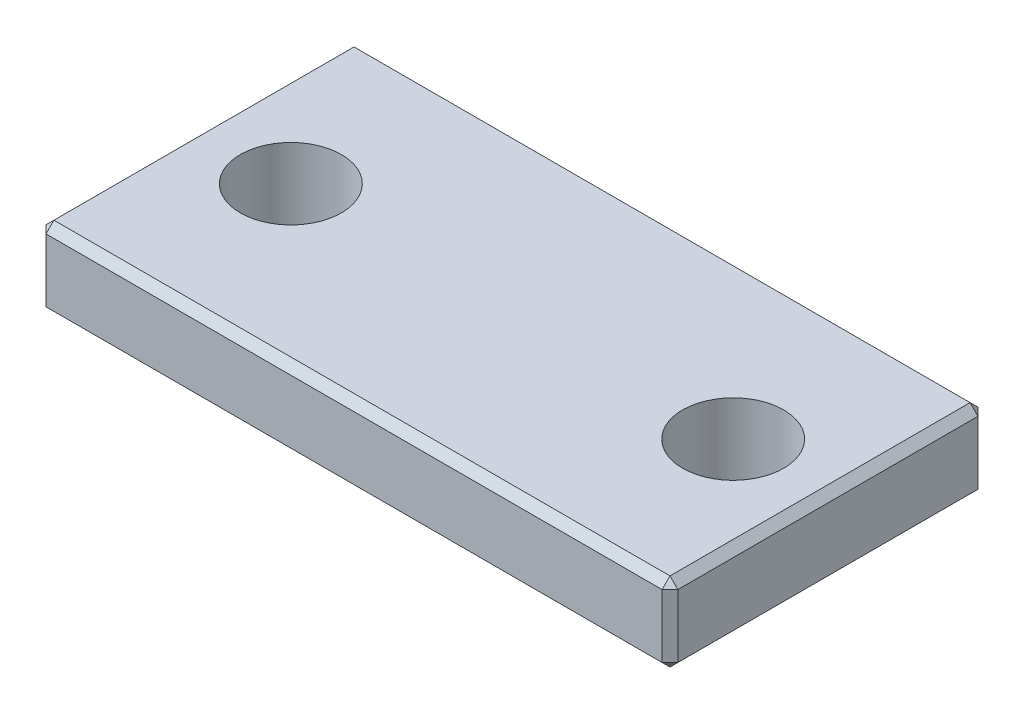
SolidWorks part; units mm, degrees
material "Plain Carbon Steel"
ref_plane "Front Plane" through (0, 0, 0) normal (0, 0, 1) x (1, 0, 0)
ref_plane "Top Plane" through (0, 0, 0) normal (0, 1, 0) x (1, 0, 0)
ref_plane "Right Plane" through (0, 0, 0) normal (1, 0, 0) x (0, 0, -1)
sketch "Sketch1" plane through (0, 0, 0) normal (0, 1, 0) x (1, 0, 0)
  line L1 (-20, -10) -> (20, -10)
  line L2 (-20, -10) -> (-20, 10)
  line L3 (-20, 10) -> (20, 10)
  line L4 (20, -10) -> (20, 10)
  line L5 (-20, -10) -> (20, 10) construction
  line L6 (-20, 10) -> (20, -10) construction
  point P0 (0, 0)
  dimension "D1" = 40
  dimension "D2" = 20
extrude "Boss-Extrude1" add sketch "Sketch1" along normal blind 5
hole_wizard "M6 Clearance Hole1" positions "Sketch4" profile "Sketch3" hole size "M6" standard "ISO" end condition through all
sketch "Sketch4" plane through (0, 5, 0) normal (0, 1, 0) x (1, 0, 0)
  line L0 (-20, 0) -> (20, 0) construction
  line L1 (-20, 10) -> (-20, -10) construction
  line L2 (20, -10) -> (20, 10) construction
  point P0 (-14, 0)
  point P2 (14, 0)
  point P13 (0, 0)
  point P14 (0, 0)
  dimension "D1" = 6
  dimension "D2" = 6
sketch "Sketch3" plane through (-14, 5, 0) normal (1, 0, 0) x (0, 0, 1)
  line L0 (0, 0) -> (0, 5)
  line L1 (0, 5) -> (3.2, 5)
  line L2 (3.2, 5) -> (3.2, 0)
  line L5 (3.2, 0) -> (0, 0)
  line L11 (0, -6.35) -> (0, 107.95) construction
  dimension "Thru Hole Dia." = 6.4
  dimension "Thru Hole Depth" = 5
chamfer "Chamfer1" distance 0.5 angle 45 12 edges at (0, 0, -10) (-20, 2.5, -10) (-20, 2.5, 10) (-20, 5, 0) (-20, 0, 0) (20, 2.5, -10) (20, 0, 0) (0, 0, 10) (20, 2.5, 10) (0, 5, -10) (20, 5, 0) (0, 5, 10)
